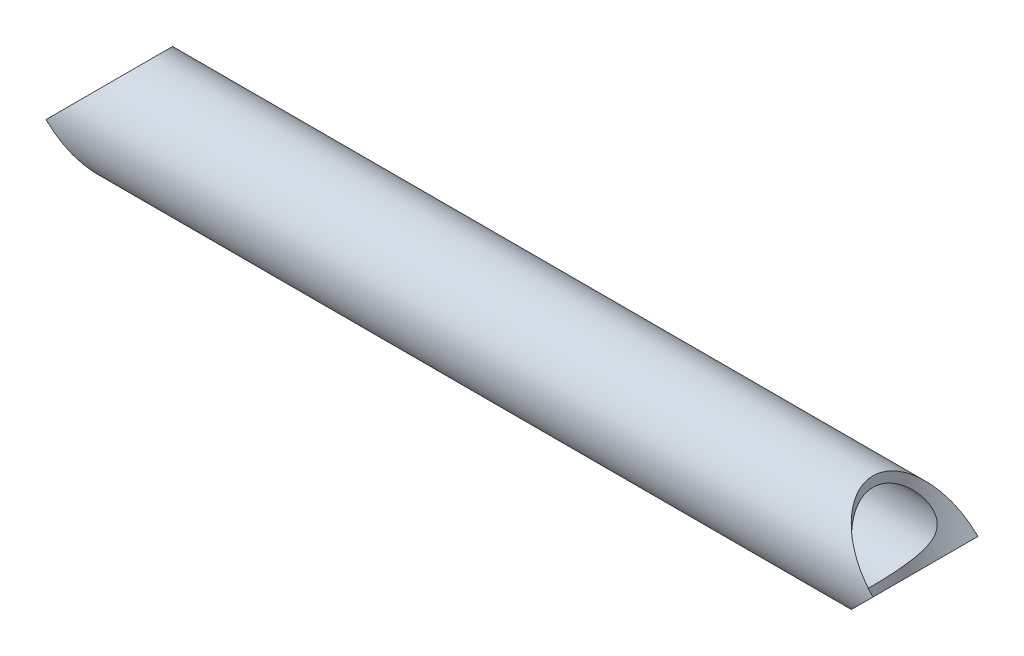
SolidWorks part; units mm, degrees
ref_plane "Front Plane" through (0, 0, 0) normal (0, 0, 1) x (1, 0, 0)
ref_plane "Top Plane" through (0, 0, 0) normal (0, 1, 0) x (1, 0, 0)
ref_plane "Right Plane" through (0, 0, 0) normal (1, 0, 0) x (0, 0, -1)
sketch "Sketch1" plane through (0, 0, 0) normal (1, 0, 0) x (0, 0, -1)
  circle A0 centre (0, 0) radius 12.7
  circle A1 centre (0, 0) radius 10.287
  dimension "D1" = 25.4
  dimension "D2" = 2.413
extrude "Boss-Extrude1" add sketch "Sketch1" along normal blind 100 and the other way blind 100
sketch "Sketch2" plane through (0, 0, 0) normal (0, 1, 0) x (1, 0, 0)
  line L0 (-100, 0) -> (100, 0) construction
  line L1 (-100, 12.7) -> (-100, -12.7) construction
  line L2 (-87.3, 0) -> (-87.3, 25.0628) construction
  line L3 (-87.3, 25.0628) -> (87.3, 25.0628) construction
  line L4 (87.3, 25.0628) -> (87.3, 0) construction
  circle A0 centre (-100, 0) radius 12.7
  circle A1 centre (100, 0) radius 12.7
  dimension "D1" = 25.4
  dimension "D2" = 200
  dimension "D3" = 174.6
  dimension "D4" = 87.3
  dimension "D5" = 87.3
extrude "Cut-Extrude1" cut sketch "Sketch2" against normal blind 50 and the other way blind 50
